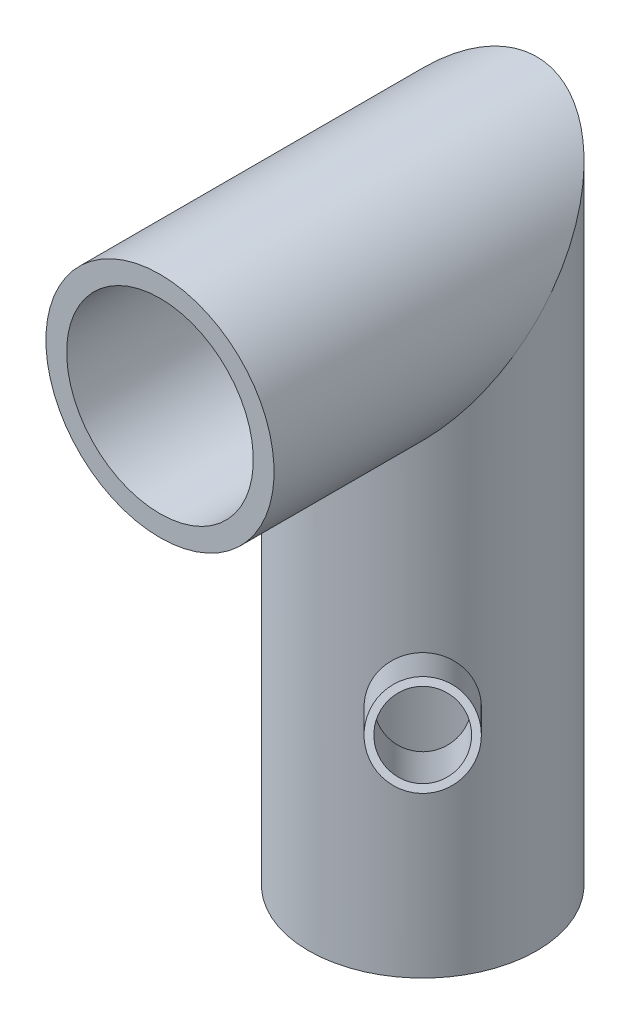
SolidWorks part; units mm, degrees
ref_plane "前视基准面" through (0, 0, 0) normal (0, 0, 1) x (1, 0, 0)
ref_plane "上视基准面" through (0, 0, 0) normal (0, 1, 0) x (1, 0, 0)
ref_plane "右视基准面" through (0, 0, 0) normal (1, 0, 0) x (0, 0, -1)
sketch "草图1" plane through (0, 0, 0) normal (1, 0, 0) x (0, 0, -1)
  line L0 (0, 0) -> (38, 0)
  line L1 (38, 0) -> (38, -79)
sweep "扫描1" add path "草图1" circular profile diameter 27 parameters "D3"=27
shell "抽壳1" thickness 3 removed face at (0, -79, -24.5) removed face at (0, -13.5, 0) outward yes
sketch "草图21" plane through (0, 0, 0) normal (1, 0, 0) x (0, 0, -1)
  line L2 (38, 0) -> (38, 9.7792)
sketch "草图23" plane through (0, 0, 0) normal (0, 1, 0) x (1, 0, 0)
  line L0 (0, 38) -> (11.6673, 26.3327)
  line L1 (0, 38) -> (21.599, 16.401)
  circle A0 centre (0, 38) radius 16.5 construction
ref_plane "基准面6" through (19, 0, -19) normal (-0.7071, 0, 0.7071) x (0.7071, 0, 0.7071)
sketch "草图24" plane through (19, 0, -19) normal (-0.7071, 0, 0.7071) x (0.7071, 0, 0.7071)
  line L0 (-14.5663, -47.6697) -> (18.2988, -28.2745)
  point P2 (0, 0)
  point P3 (-17.8108, -49.5861)
  point P4 (-12.9516, -46.1021)
  point P5 (0, 0)
  point P6 (-14.5663, -47.6697)
sweep "扫描2" add path "草图24" circular profile diameter 12 parameters "D3"=12
ref_plane "基准面7" through (0.8457, 0.7059, 0.8457) normal (0.609, 0.5082, 0.609) x (0.7932, -0.3902, -0.4675)
sketch "草图46" plane through (0.8457, 0.7059, 0.8457) normal (0.609, 0.5082, 0.609) x (0.7932, -0.3902, -0.4675)
  circle A0 centre (39.2003, -17.8241) radius 5
extrude "切除-拉伸1" cut sketch "草图46" against normal blind 44
